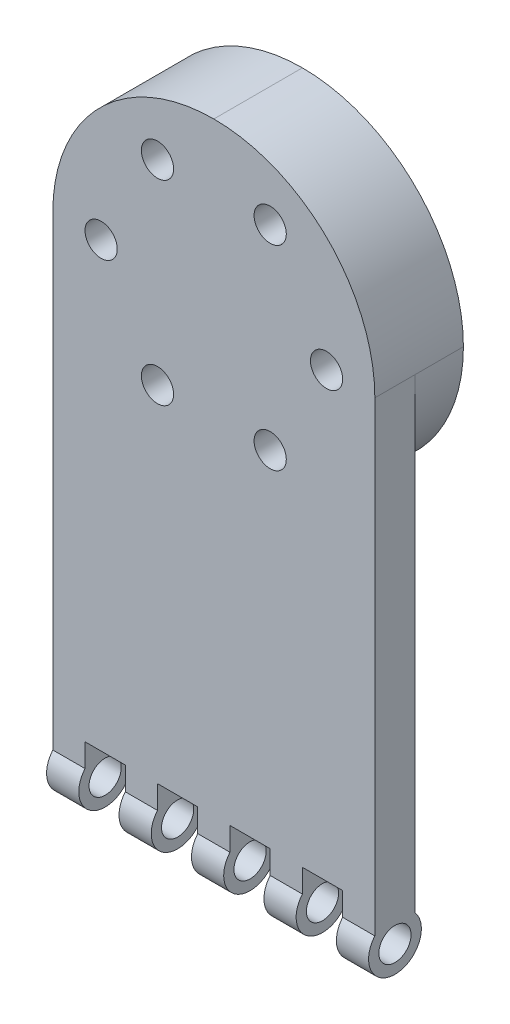
SolidWorks part; units mm, degrees
other "Markup1"
sketch "Sketch13" plane through (20, -53, 11) normal (0.0614, -0.6805, 0.7302) x (0.9699, -0.1321, -0.2046)
ref_plane "Front Plane" through (0, 0, 0) normal (0, 0, 1) x (1, 0, 0)
ref_plane "Top Plane" through (0, 0, 0) normal (0, 1, 0) x (1, 0, 0)
ref_plane "Right Plane" through (0, 0, 0) normal (1, 0, 0) x (0, 0, -1)
sketch "Sketch7" plane through (0, 0, 0) normal (0, 0, 1) x (1, 0, 0)
  line L1 (-20, 20) -> (20, 20)
  line L2 (-20, 20) -> (-20, -20)
  line L3 (-20, -20) -> (20, -20)
  line L4 (20, 20) -> (20, -20)
  line L5 (-20, 20) -> (20, -20) construction
  line L6 (-20, -20) -> (20, 20) construction
  point P0 (0, 0)
extrude "Boss-Extrude1" add sketch "Sketch7" along normal blind 11
sketch "Sketch8" plane through (0, -20, 0) normal (0, -1, 0) x (1, 0, 0)
  line L0 (20, 11) -> (20, 0) construction
  line L1 (-20, 11) -> (20, 11)
  line L2 (-20, 11) -> (-20, 6)
  line L3 (-20, 6) -> (20, 6)
  line L4 (20, 11) -> (20, 6)
  line L5 (0, 6) -> (0, 11) construction
  line L6 (-20, 8.5) -> (20, 8.5) construction
  point P764 (0, 8.5)
extrude "Boss-Extrude2" add sketch "Sketch8" along normal blind 35
sketch "Sketch10" plane through (0, 0, 11) normal (0, 0, 1) x (1, 0, 0)
  circle A0 centre (-7.0001, 12.1244) radius 2
  circle A1 centre (6.9999, 12.1244) radius 2
  circle A2 centre (13.9999, 0.0001) radius 2
  circle A3 centre (6.9999, -12.1243) radius 2
  circle A4 centre (-7.0001, -12.1243) radius 2
  circle A5 centre (-14.0001, 0.0001) radius 2
  point P0 (0, 0)
  point P1 (0.0025, 0.0011)
  dimension "D1" = 4
  dimension "D2" = 4
  dimension "D3" = 4
  dimension "D4" = 4
  dimension "D5" = 4
  dimension "D6" = 4
extrude "Cut-Extrude1" cut sketch "Sketch10" against normal blind 25
fillet "Fillet1" radius 20 4 edges at (20, -20, 3) (20, 20, 5.5) (-20, 20, 5.5) (-20, -20, 3)
sketch "Sketch11" plane through (0, -55, 0) normal (0, -1, 0) x (1, 0, 0)
  line L0 (-20, 6) -> (20, 6) construction
  line L1 (-20, 11) -> (-16, 11)
  line L2 (-20, 11) -> (-20, 6)
  line L3 (-20, 6) -> (-16, 6)
  line L4 (-16, 11) -> (-16, 6)
  line L5 (-18, 6) -> (-18, 11) construction
  line L6 (-20, 8.5) -> (-16, 8.5) construction
  point P368 (-18, 8.5)
extrude "Boss-Extrude3" add sketch "Sketch11" along normal blind 6 contours L1 L4 L3 L2
ref_plane "Plane1" through (-16, 0, 0) normal (1, 0, 0) x (0, 0, -1)
sketch "Sketch14" plane through (-16, 0, 0) normal (1, 0, 0) x (0, 0, -1)
  line L0 (-11, -61) -> (-6, -61) construction
  line L1 (-11, 0) -> (-11, -61) construction
  circle A0 centre (-8.5, -60) radius 3.2762
  point P2 (-8.3584, -60.2809)
  point P3 (-8.3529, -61.5276)
  point P4 (-8.0634, -59.5066)
  dimension "D1" = 1
  dimension "D2" = 2.5
extrude "Boss-Extrude4" add sketch "Sketch14" against normal up to vertex (4 mm away) up to point (-20, -61, 11)
pattern_linear "LPattern1" count 5 spacing 9 along (1, 0, 0) of "Boss-Extrude4", "Boss-Extrude3"
sketch "Sketch15" plane through (-20, 0, 0) normal (-1, 0, 0) x (0, 0, 1)
  circle A0 centre (8.5, -60) radius 2
extrude "Cut-Extrude2" cut sketch "Sketch15" against normal through all
